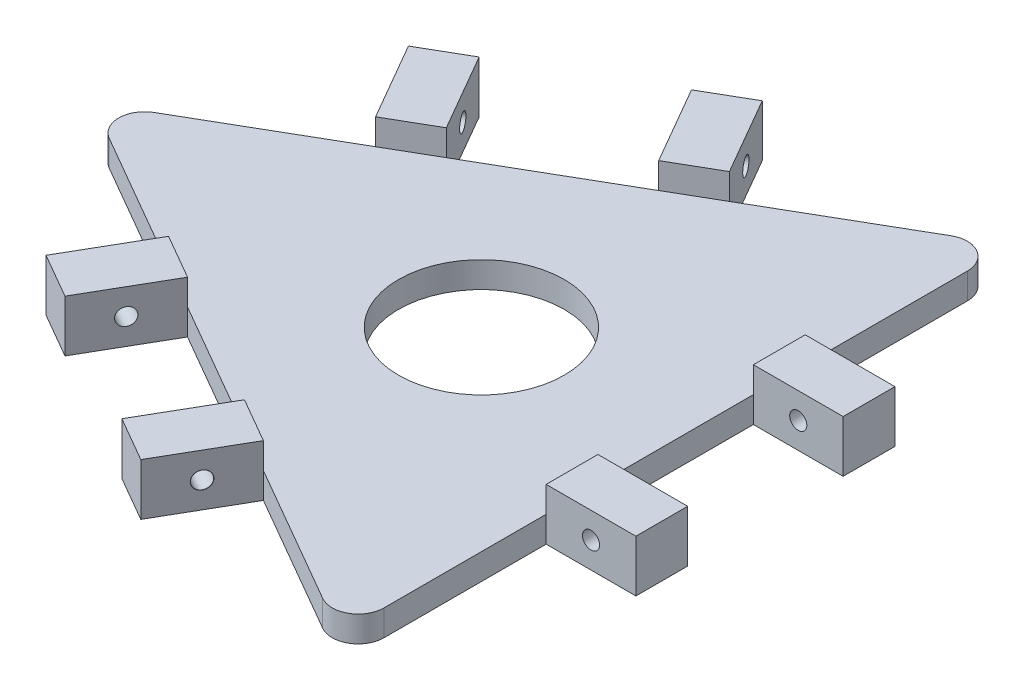
SolidWorks part; units mm, degrees
material "ABS"
ref_plane "Front" through (0, 0, 0) normal (0, 0, 1) x (1, 0, 0)
ref_plane "Top" through (0, 0, 0) normal (0, 1, 0) x (1, 0, 0)
ref_plane "Right" through (0, 0, 0) normal (1, 0, 0) x (0, 0, -1)
sketch "Sketch2" plane through (0, 0, 0) normal (0, 1, 0) x (0, 0, -1)
  line L0 (0, 0) -> (0, 70) construction
  line L1 (0, 0) -> (-60.6218, -35) construction
  line L2 (-60.6218, -30) -> (-44.976, -2.9006)
  line L3 (4.3301, 67.5) -> (19.976, 40.4006)
  line L4 (56.2917, -37.5) -> (25, -37.5)
  line L5 (0, 0) -> (-23.8157, 13.75) construction
  line L9 (-44.976, -2.9006) -> (-59.976, 5.7596)
  line L10 (-39.976, 5.7596) -> (-54.976, 14.4199)
  line L11 (-59.976, 5.7596) -> (-54.976, 14.4199)
  line L12 (-24.976, 31.7404) -> (-39.976, 40.4006)
  line L13 (-34.976, 49.0609) -> (-39.976, 40.4006)
  line L14 (-19.976, 40.4006) -> (-34.976, 49.0609)
  line L17 (19.976, 40.4006) -> (34.976, 49.0609)
  line L18 (34.976, 49.0609) -> (39.976, 40.4006)
  line L19 (24.976, 31.7404) -> (39.976, 40.4006)
  line L20 (39.976, 5.7596) -> (54.976, 14.4199)
  line L21 (59.976, 5.7596) -> (54.976, 14.4199)
  line L22 (44.976, -2.9006) -> (59.976, 5.7596)
  line L25 (25, -37.5) -> (25, -54.8205)
  line L26 (25, -54.8205) -> (15, -54.8205)
  line L27 (15, -37.5) -> (15, -54.8205)
  line L28 (-25, -37.5) -> (-25, -54.8205)
  line L29 (-25, -54.8205) -> (-15, -54.8205)
  line L30 (-15, -37.5) -> (-15, -54.8205)
  line L32 (-39.976, 5.7596) -> (-24.976, 31.7404)
  line L33 (-19.976, 40.4006) -> (-4.3301, 67.5)
  line L34 (24.976, 31.7404) -> (39.976, 5.7596)
  line L35 (44.976, -2.9006) -> (60.6218, -30)
  line L36 (15, -37.5) -> (-15, -37.5)
  line L37 (-25, -37.5) -> (-56.2917, -37.5)
  line L38 (-44.976, -2.9006) -> (-39.976, 5.7596)
  line L39 (-19.976, 40.4006) -> (-24.976, 31.7404)
  line L40 (19.976, 40.4006) -> (24.976, 31.7404)
  line L41 (44.976, -2.9006) -> (39.976, 5.7596)
  line L42 (25, -37.5) -> (15, -37.5)
  line L43 (-25, -37.5) -> (-15, -37.5)
  line L44 (-51.0586, -4.4382) -> (-50.8563, -4.8955) construction
  line L45 (-29.695, -52.7232) -> (-29.4927, -53.1804) construction
  line L46 (-29.695, -52.7232) -> (-32.1834, -47.0991) construction
  line L47 (-50.8563, -4.8955) -> (-48.368, -10.5196) construction
  line L48 (-51.0586, -4.4382) -> (-50.8563, -4.8955)
  line L49 (-29.695, -52.7232) -> (-29.4927, -53.1804)
  line L50 (-29.695, -52.7232) -> (-32.1834, -47.0991)
  line L51 (-50.8563, -4.8955) -> (-48.368, -10.5196)
  line L57 (-65.1075, -34.9031) -> (-35.2275, -21.6827) construction
  line L58 (-71.5306, -20.3861) -> (-55.0635, -57.6041) construction
  line L59 (-36.1997, -19.4853) -> (-25.527, -43.6072) construction
  arc A0 (-60.6218, -30) -> (-56.2917, -37.5) centre (-56.2917, -32.5) ccw
  arc A1 (60.6218, -30) -> (56.2917, -37.5) centre (56.2917, -32.5) cw
  arc A2 (4.3301, 67.5) -> (-4.3301, 67.5) centre (0, 65) ccw
  circle A3 centre (-56.2917, -32.5) radius 5 construction
  dimension "D4" = 10
  dimension "D1" = 90
  dimension "D2" = 50
  dimension "D3" = 70
  dimension "D7" = 10
  dimension "D8" = 15
extrude "Boss-Extrude1" add sketch "Sketch2" along normal blind 5 contours L3 A2 L33 L39 L32 L38 L2 A0 L37 L43 L36 L42 L4 A1 L35 L41 L34 L40
extrude "Boss-Extrude3" add sketch "Sketch2<7>" along normal blind 10 contours L41 L22 L21 L20 | L17 L40 L19 L18 region at (-40.4006, 0, -29.976) region at (-5.7596, 0, -49.976)
sketch "Sketch2<7>" plane through (0, 0, 0) normal (0, 1, 0) x (0, 0, -1) same geometry as "Sketch2"
sketch "Sketch10" plane through (-21.6506, 0, 12.5) normal (-0.866, 0, 0.5) x (0.5, 0, 0.866)
  line L1 (-46.1603, 5) -> (-37.5, 5) construction
  line L2 (-54.8205, 5) -> (-46.1603, 5) construction
  line L9 (-54.8205, 10) -> (-54.8205, 0) construction
  line L11 (-46.1603, 5) -> (-46.1603, 10) construction
  line L12 (-37.5, 10) -> (-54.8205, 10) construction
  line L14 (-46.1603, 5) -> (-46.1603, 0) construction
  line L15 (-37.5, 0) -> (-54.8205, 0) construction
  point P0 (-46.1603, 5)
  dimension "D1" = 180
hole_wizard "Tap Drill for M4 Tap1" positions "Sketch10" profile "Sketch11" hole size "M4" standard "ISO" end condition through all
sketch "Sketch11" plane through (-44.7308, 5, -27.476) normal (0, 1, 0) x (0.5, 0, 0.866)
  line L0 (0, 0) -> (0, 88.1218)
  line L1 (0, 88.1218) -> (1.65, 88.1218)
  line L2 (1.65, 88.1218) -> (1.65, 0.025)
  line L3 (1.65, 0.025) -> (1.675, 0)
  line L5 (1.675, 0) -> (0, 0)
  line L6 (-1.65, 0.025) -> (-1.675, 0) construction
  line L11 (0, -6.35) -> (0, 107.95) construction
  dimension "Thru Hole Dia." = 3.3
  dimension "Thru Hole Depth" = 88.1218
  dimension "Near C'Sink Dia." = 3.35
  dimension "Near C'Sink Angle" = 90
pattern_circular "CirPattern1" count 3 every 120 about axis through (0, 5, 0) along (0, 1, 0) of "Boss-Extrude3", "Tap Drill for M4 Tap1"
sketch "Sketch13" plane through (0, 0, 0) normal (0, -1, 0) x (1, 0, 0)
  line L0 (-18.75, 32.476) -> (0, 0) construction
  line L1 (0, 0) -> (37.5, 0) construction
  line L2 (-5.7596, 39.976) -> (-31.7404, 24.976) construction
  line L3 (37.5, -15) -> (37.5, 15) construction
  line L4 (-31.7404, -24.976) -> (-5.7596, -39.976) construction
  line L5 (0, 0) -> (-18.75, -32.476) construction
  circle A2 centre (0, 0) radius 16
  point P3 (0, 0)
  point P4 (-18.75, 32.476)
  point P5 (37.5, 0)
  point P8 (-18.75, -32.476)
  dimension "D1" = 32
extrude "Cut-Extrude1" cut sketch "Sketch13" against normal through all contours A2
